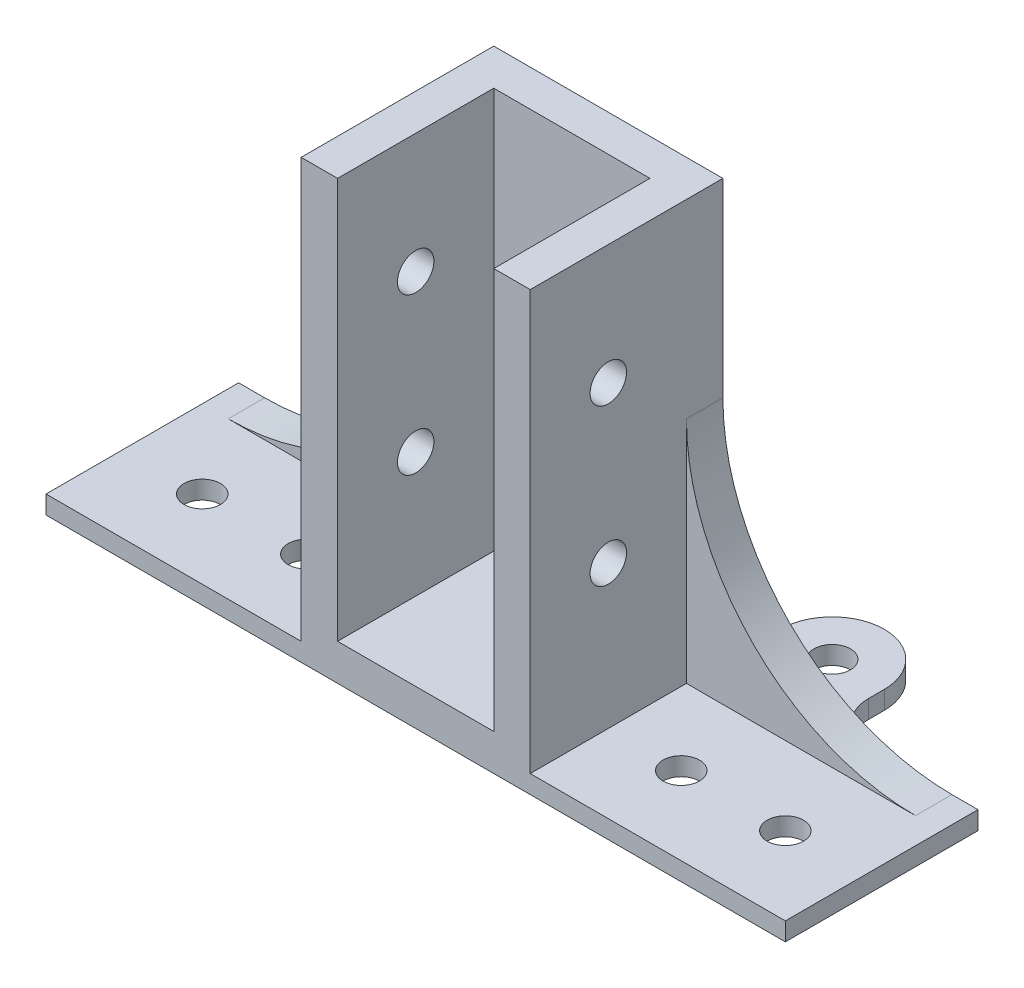
SolidWorks part; units mm, degrees
ref_plane "Front Plane" through (0, 0, 0) normal (0, 0, 1) x (1, 0, 0)
ref_plane "Top Plane" through (0, 0, 0) normal (0, 1, 0) x (1, 0, 0)
ref_plane "Right Plane" through (0, 0, 0) normal (1, 0, 0) x (0, 0, -1)
sketch "Sketch1" plane through (0, 0, 0) normal (0, 0, 1) x (1, 0, 0)
  line L1 (-16.1393, 44.8689) -> (5.8607, 44.8689)
  line L2 (-16.1393, 44.8689) -> (-16.1393, 2.8689)
  line L3 (-16.1393, 2.8689) -> (5.8607, 2.8689)
  line L4 (5.8607, 44.8689) -> (5.8607, 2.8689)
  dimension "D1" = 22
  dimension "D2" = 42
extrude "Boss-Extrude1" add sketch "Sketch1" along normal blind 18.5
sketch "Sketch2" plane through (0, 0, 18.5) normal (0, 0, 1) x (1, 0, 0)
  line L0 (5.8607, 44.8689) -> (-16.1393, 44.8689) construction
  line L1 (-12.6393, 44.8689) -> (2.3607, 44.8689)
  line L2 (-12.6393, 44.8689) -> (-12.6393, 6.3689)
  line L3 (-12.6393, 6.3689) -> (2.3607, 6.3689)
  line L4 (2.3607, 44.8689) -> (2.3607, 6.3689)
  line L5 (5.8607, 2.8689) -> (5.8607, 44.8689) construction
  line L6 (-16.1393, 2.8689) -> (5.8607, 2.8689) construction
  dimension "D1" = 15
  dimension "D2" = 3.5
  dimension "D3" = 3.5
extrude "Cut-Extrude1" cut sketch "Sketch2" against normal blind 15
sketch "Sketch3" plane through (0, 0, 0) normal (0, 0, -1) x (-1, 0, 0)
  line L1 (16.1393, 2.8689) -> (40.6393, 2.8689)
  line L2 (16.1393, 2.8689) -> (16.1393, 4.6189)
  line L3 (16.1393, 4.6189) -> (40.6393, 4.6189)
  line L4 (40.6393, 2.8689) -> (40.6393, 4.6189)
  line L5 (-5.8607, 2.8689) -> (-30.3607, 2.8689)
  line L6 (-5.8607, 2.8689) -> (-5.8607, 4.6189)
  line L7 (-5.8607, 4.6189) -> (-30.3607, 4.6189)
  line L8 (-30.3607, 2.8689) -> (-30.3607, 4.6189)
  dimension "D1" = 24.5
  dimension "D2" = 24.5
  dimension "D3" = 1.75
  dimension "D4" = 1.75
extrude "Boss-Extrude2" add sketch "Sketch3" against normal up to surface (18.5 mm away) up to face at (-5.1393, 24.7439, 18.5)
sketch "Sketch4" plane through (0, 0, 0) normal (0, 0, -1) x (-1, 0, 0)
  line L0 (38.1393, 4.6189) -> (16.1393, 4.6189)
  line L1 (40.6393, 4.6189) -> (16.1393, 4.6189) construction
  line L2 (16.1393, 4.6189) -> (16.1393, 26.6189)
  line L3 (16.1393, 44.8689) -> (16.1393, 4.6189) construction
  line L4 (-27.8607, 4.6189) -> (-5.8607, 4.6189)
  line L5 (-5.8607, 4.6189) -> (-30.3607, 4.6189) construction
  line L6 (-5.8607, 4.6189) -> (-5.8607, 26.6189)
  line L7 (-5.8607, 4.6189) -> (-5.8607, 44.8689) construction
  arc A0 (16.1393, 26.6189) -> (38.1393, 4.6189) centre (38.1393, 26.6189) ccw
  arc A1 (-5.8607, 26.6189) -> (-27.8607, 4.6189) centre (-27.8607, 26.6189) cw
  dimension "D1" = 22
extrude "Boss-Extrude3" add sketch "Sketch4" against normal blind 3.5
sketch "Sketch5" plane through (0, 2.8689, 0) normal (0, -1, 0) x (1, 0, 0)
  line L0 (-40.6393, 0) -> (30.3607, 0) construction
  line L1 (5.8607, 0) -> (-16.1393, 0) construction
  line L2 (15.8607, -5.5) -> (15.8607, 0)
  line L3 (-26.1393, -5.5) -> (-26.1393, 0)
  line L4 (-16.1393, -5.5) -> (-16.1393, 0)
  line L5 (5.8607, -5.5) -> (5.8607, 0)
  line L6 (15.8607, 0) -> (5.8607, 0)
  line L7 (-16.1393, 0) -> (-26.1393, 0)
  circle A0 centre (10.8607, -5.5) radius 1.75
  circle A1 centre (-21.1393, -5.5) radius 1.75
  arc A2 (5.8607, -5.5) -> (15.8607, -5.5) centre (10.8607, -5.5) ccw
  arc A3 (-26.1393, -5.5) -> (-16.1393, -5.5) centre (-21.1393, -5.5) ccw
  point P6 (-5.1393, 0)
  point P7 (-5.1393, 0)
  dimension "D4" = 3.5
  dimension "D1" = 5.5
  dimension "D2" = 16
  dimension "D3" = 16
extrude "Boss-Extrude4" add sketch "Sketch5" against normal up to surface (1.75 mm away) up to face at (-33.8893, 4.6189, 8.5833)
sketch "Sketch6" plane through (0, 4.6189, 0) normal (0, 1, 0) x (1, 0, 0)
  line L0 (30.3607, -11) -> (-40.6393, -11) construction
  line L1 (30.3607, -18.5) -> (30.3607, 0) construction
  line L2 (-40.6393, -18.5) -> (-40.6393, 0) construction
  line L3 (5.8607, -18.5) -> (30.3607, -18.5) construction
  circle A0 centre (22.8607, -11) radius 1.75
  circle A1 centre (-33.1393, -11) radius 1.75
  circle A2 centre (12.8607, -11) radius 1.75
  circle A3 centre (-23.1393, -11) radius 1.75
  dimension "D2" = 7.5
  dimension "D3" = 7.5
  dimension "D4" = 3.5
  dimension "D5" = 10
  dimension "D6" = 10
  dimension "D1" = 7.5
extrude "Cut-Extrude2" cut sketch "Sketch6" against normal blind 10
fillet "Fillet1" radius 4 4 edges at (-26.1393, 3.7439, 0) (-16.1393, 3.7439, 0)
sketch "Sketch7" plane through (-16.1393, 0, 0) normal (-1, 0, 0) x (0, 0, 1)
  line L0 (11, 44.8689) -> (11, 4.6189) construction
  line L1 (18.5, 44.8689) -> (0, 44.8689) construction
  line L2 (18.5, 4.6189) -> (0, 4.6189) construction
  line L3 (18.5, 44.8689) -> (18.5, 4.6189) construction
  line L4 (3.5, 6.3689) -> (18.5, 6.3689) construction
  circle A0 centre (11, 33.3689) radius 1.75
  circle A1 centre (11, 18.3689) radius 1.75
  dimension "D2" = 3.5
  dimension "D1" = 7.5
  dimension "D3" = 15
  dimension "D4" = 12
extrude "Cut-Extrude3" cut sketch "Sketch7" against normal blind 28
sketch "Sketch8" plane through (0, 0, 0) normal (0, 0, -1) x (-1, 0, 0)
  line L0 (5.1393, 44.8689) -> (5.1393, 2.8689) construction
  line L1 (-5.8607, 44.8689) -> (16.1393, 44.8689) construction
  line L2 (12.1393, 2.8689) -> (-1.8607, 2.8689) construction
  line L3 (12.6393, 6.3689) -> (-2.3607, 6.3689) construction
  circle A0 centre (5.1393, 33.3689) radius 1.75
  circle A1 centre (5.1393, 18.3689) radius 1.75
  dimension "D1" = 15
  dimension "D2" = 12
  dimension "D3" = 3.5
extrude "Cut-Extrude4" cut sketch "Sketch8" against normal blind 28
